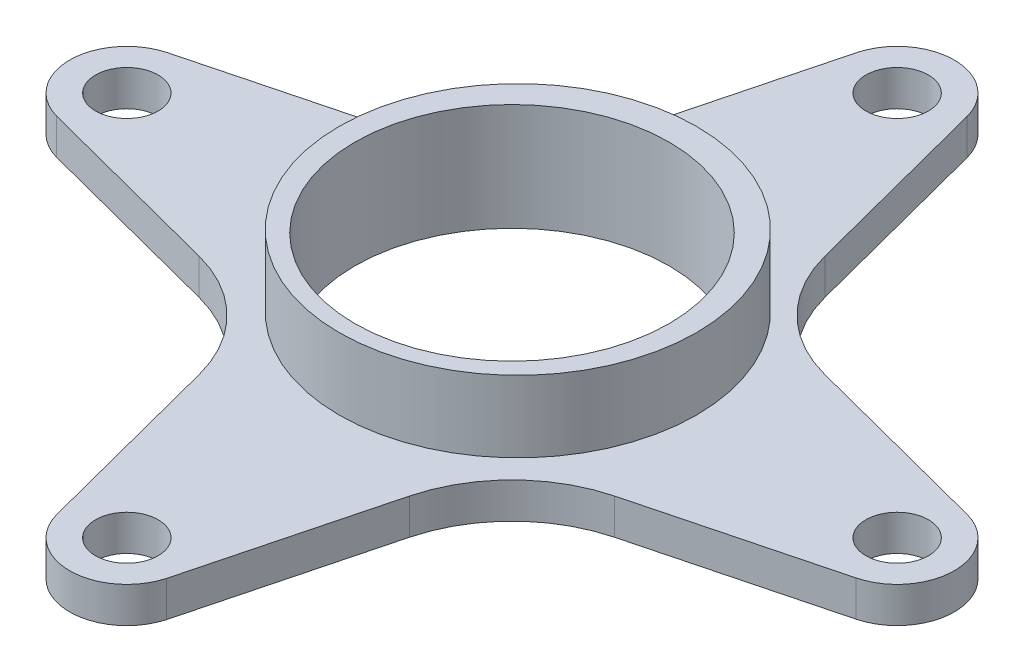
SolidWorks part; units mm, degrees
ref_plane "Front Plane" through (0, 0, 0) normal (0, 0, 1) x (1, 0, 0)
ref_plane "Top Plane" through (0, 0, 0) normal (0, 1, 0) x (1, 0, 0)
ref_plane "Right Plane" through (0, 0, 0) normal (1, 0, 0) x (0, 0, -1)
sketch "Sketch1" plane through (0, 0, 0) normal (0, 1, 0) x (1, 0, 0)
  line L0 (0, 68.4524) -> (0, 0) construction
  line L1 (0, 0) -> (37.992, 37.992) construction
  line L2 (0, 0) -> (-32.2088, 32.2088) construction
  line L3 (-18.6973, 36.8926) -> (-9.7793, 71.2077)
  line L4 (9.8335, 71.0075) -> (18.6979, 36.8928)
  line L5 (71.0075, -9.8335) -> (36.8928, -18.6979)
  line L6 (36.8926, 18.6973) -> (71.2077, 9.7793)
  line L7 (-9.8335, -71.0075) -> (-18.6979, -36.8928)
  line L8 (18.6973, -36.8926) -> (9.7793, -71.2077)
  line L9 (-71.0075, 9.8335) -> (-36.8928, 18.6979)
  line L10 (-36.8926, -18.6973) -> (-71.2077, -9.7793)
  circle A0 centre (0, 0) radius 31.75
  circle A1 centre (0, 68.4524) radius 5.5562
  circle A2 centre (0, 68.4524) radius 10.16
  circle A3 centre (68.4524, 0) radius 10.16
  circle A4 centre (68.4524, 0) radius 5.5563
  circle A5 centre (0, -68.4524) radius 10.16
  circle A6 centre (0, -68.4524) radius 5.5563
  circle A7 centre (-68.4524, 0) radius 10.16
  circle A8 centre (-68.4524, 0) radius 5.5563
  arc A9 (18.6979, 36.8928) -> (36.8926, 18.6973) centre (43.2816, 43.2807) ccw
  arc A10 (36.8928, -18.6979) -> (18.6973, -36.8926) centre (43.2807, -43.2816) ccw
  arc A11 (-18.6979, -36.8928) -> (-36.8926, -18.6973) centre (-43.2816, -43.2807) ccw
  arc A12 (-18.6973, 36.8926) -> (-36.8928, 18.6979) centre (-43.2807, 43.2816) cw
  circle A13 centre (0, 0) radius 27.94
  point P14 (22.4506, 22.4506)
  point P36 (0, 0)
  point P39 (-22.4506, 22.4506)
  dimension "D1" = 90
  dimension "D4" = 25.4
  dimension "D2" = 45
  dimension "D3" = 4
extrude "Boss-Extrude1" add sketch "Sketch1" along normal blind 6.35 contours A7 L10 A8 | L3 A12 L9 A7 L10 A11 L7 A5 L8 A10 L5 A3 L6 A9 L4 A2 A0 | L8 A5 A6 | A2 L3 A1 | A3 L6 A4 | A0 A13 region at (-12.3465, 0, -53.3447) region at (-9.5532, 0, -70.9351) region at (-62.4127, 0, -7.8097) region at (70.9351, 0, -9.5532) region at (-1.2515, 0, 58.6594) region at (-30.852, 0, 0)
sketch "Sketch2" plane through (0, 6.35, 0) normal (0, 1, 0) x (1, 0, 0)
  circle A0 centre (0, 0) radius 27.94
  circle A1 centre (0, 1.0384) radius 31.75
extrude "Boss-Extrude2" add sketch "Sketch2" along normal blind 12.7
